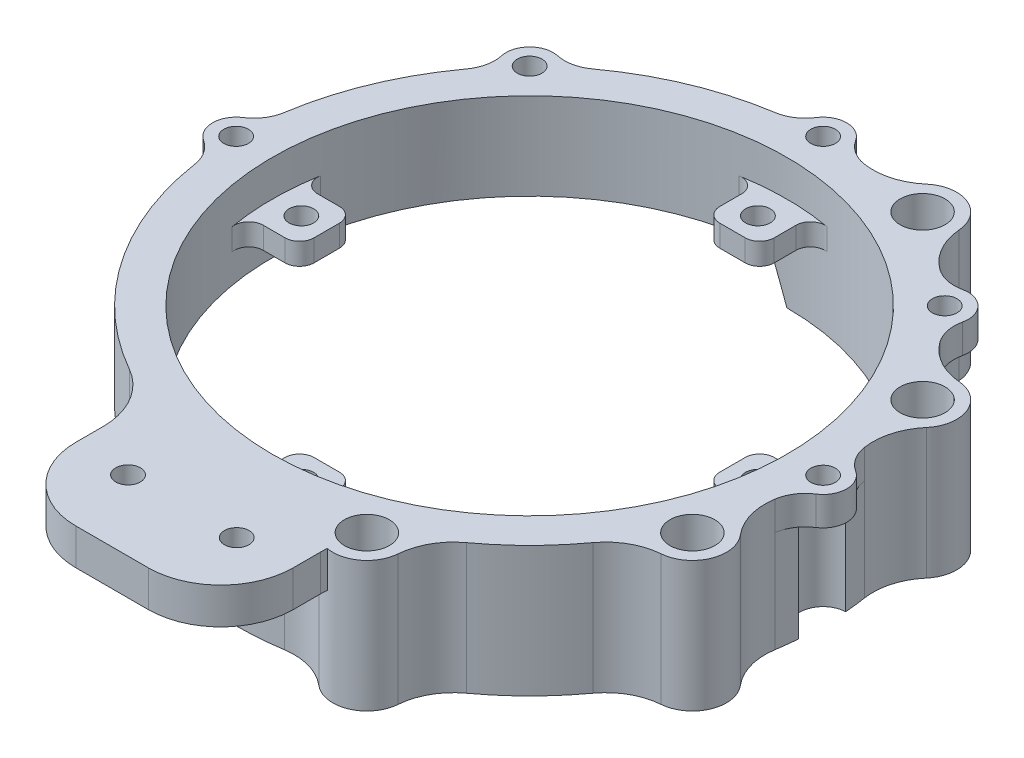
SolidWorks part; units mm, degrees
ref_plane "Alzado" through (0, 0, 0) normal (0, 0, 1) x (1, 0, 0)
ref_plane "Planta" through (0, 0, 0) normal (0, 1, 0) x (1, 0, 0)
ref_plane "Vista lateral" through (0, 0, 0) normal (1, 0, 0) x (0, 0, -1)
sketch "Croquis1" plane through (0, 0, 0) normal (0, 1, 0) x (1, 0, 0)
  circle A0 centre (0, 0) radius 35.5
  circle A1 centre (0, 0) radius 40.5
  dimension "D1" = 71
  dimension "D2" = 5
extrude "Saliente-Extruir1" add sketch "Croquis1" along normal mid plane 18
sketch "Croquis2" plane through (0, 9, 0) normal (0, -1, 0) x (1, 0, 0)
  line L0 (-15, 37.6198) -> (-15, 57.6198)
  line L1 (-15, 57.6198) -> (15, 57.6198)
  line L2 (15, 57.6198) -> (15, 37.6198)
  line L3 (0, 0) -> (0, 98.2113) construction
  circle A0 centre (0, 0) radius 40.5 construction
  arc A1 (15, 37.6198) -> (-15, 37.6198) centre (0, 0) ccw
  circle A2 centre (-7.5, 47.9166) radius 1.7
  circle A3 centre (7.5, 47.9166) radius 1.7
  circle A6 centre (0, 0) radius 48.5
  circle A7 centre (0, 0) radius 48.5 construction
  point P7 (0, 57.6198)
  dimension "D5" = 3.4
  dimension "D1" = 30
  dimension "D2" = 20
  dimension "D3" = 8
  dimension "D4" = 15
extrude "Saliente-Extruir2" add sketch "Croquis2" along normal blind 5
fillet "Redondeo1" radius 10 4 edges at (15, 6.5, 37.6198) (-15, 6.5, 37.6198) (-15, 6.5, 57.6198) (15, 6.5, 57.6198)
ref_plane "Plano1" through (0, 1, 0) normal (0, -1, 0) x (-1, 0, 0)
sketch "Croquis4" plane through (0, 1, 0) normal (0, -1, 0) x (-1, 0, 0)
  line L0 (0, -35.5) -> (0, 0) construction
  line L1 (-3.75, -35.3014) -> (-3.75, -28)
  line L2 (-3.75, -28) -> (3.75, -28)
  line L3 (3.75, -35.3014) -> (3.75, -28)
  circle A0 centre (0, 0) radius 35.5 construction
  arc A1 (-3.75, -35.3014) -> (3.75, -35.3014) centre (0, 0) ccw
  circle A2 centre (0, 0) radius 25 construction
  circle A3 centre (0, -31.5) radius 1.7
  circle A4 centre (0, 0) radius 31.5 construction
  point P12 (0, -28)
  dimension "D1" = 3.4
  dimension "D5" = 50
  dimension "D6" = 6.5
  dimension "D3" = 7.5
  dimension "D4" = 3.75
extrude "Saliente-Extruir3" add sketch "Croquis4" against normal blind 3
fillet "Redondeo2" radius 2 4 edges at (-3.75, 2.5, 35.3014) (3.75, 2.5, 28) (-3.75, 2.5, 28) (3.75, 2.5, 35.3014)
pattern_circular "MatrizC1" count 4 over 360 about axis through (0, 9, 0) along (0, 1, 0) of "Saliente-Extruir3", "Redondeo2"
hole_wizard "Refrentado para tornillo con cabeza plana de M31" positions "Croquis5" profile "Croquis7" counterbore size "M3" standard "ISO" end condition through all
sketch "Croquis5" plane through (0, -9, 0) normal (0, -1, 0) x (-1, 0, 0)
  circle A0 centre (0, 0) radius 40.5 construction
  point P0 (0, 40.5)
sketch "Croquis7" plane through (0, -9, -40.5) normal (1, 0, 0) x (0, 0, -1)
  line L0 (0, 0) -> (0, 18)
  line L1 (0, 18) -> (1.7, 18)
  line L3 (1.7, 18) -> (1.7, 14)
  line L4 (1.7, 14) -> (3.25, 14)
  line L5 (3.25, 14) -> (3.25, 0)
  line L7 (3.25, 0) -> (0, 0)
  line L11 (0, -6.35) -> (0, 107.95) construction
  dimension "Diámetro de taladro hasta el siguiente" = 3.4
  dimension "Profundidad de taladro hasta el siguiente" = 18
  dimension "Diámetro de refrentado" = 6.5
  dimension "Profundidad de refrentado" = 14
sketch "Croquis8" plane through (0, 5, 0) normal (0, -1, 0) x (1, 0, 0)
  circle A0 centre (0, -40.5) radius 3.25
  circle A2 centre (0, -40.5) radius 1.7
extrude "Saliente-Extruir4" add sketch "Croquis8" against normal up to surface (4 mm away) up to face at (0, 9, 27.8312)
pattern_circular "MatrizC2" count 3 every 45 about axis through (0, -9, 0) along (0, 1, 0) of "Saliente-Extruir4", "Refrentado para tornillo con cabeza plana de M31"
mirror "Simetría1" about plane through (0, 0, 0) normal (1, 0, 0) of "MatrizC2"
fillet "Redondeo4" radius 5 10 edges at (-40.3696, 7, -3.2474) (-40.3696, 7, 3.2474) (-30.8419, 7, -26.2494) (-26.2494, 7, -30.8419) (-3.2474, 7, -40.3696) (3.2474, 7, -40.3696) (40.3696, 7, -3.2474) (40.3696, 7, 3.2474) (30.8419, 7, -26.2494) (26.2494, 7, -30.8419)
sketch "Croquis13" plane through (0, -9, 0) normal (0, -1, 0) x (1, 0, 0)
  line L0 (0, 40.5) -> (0, 35.5)
  line L1 (0, -35.5) -> (0, -40.5)
  arc A0 (0, 40.5) -> (0, -40.5) centre (0, 0) ccw
  arc A1 (0, 35.5) -> (0, -35.5) centre (0, 0) ccw
  dimension "D1" = 81
extrude "Cortar-Extruir5" cut sketch "Croquis13" against normal blind 6
chamfer "Chaflán1" distance 6 angle 20 2 edges at (0, -3, -36.375) (0, -3, 38) first distance on face at (0, -6, -36.375) first distance on face at (0, -6, 38)
sketch "Croquis14" plane through (0, -9, 0) normal (0, -1, 0) x (1, 0, 0)
  line L0 (19.8796, 0) -> (0, 0) construction
  line L1 (0, 0) -> (11.2108, 27.0652) construction
  line L2 (0, 0) -> (11.2108, -27.0652) construction
  circle A0 centre (15.8814, 38.341) radius 1.7
  circle A1 centre (0, 0) radius 40.5 construction
  circle A8 centre (38.1004, 15.9815) radius 1.7
  circle A9 centre (38.0004, -15.5403) radius 1.7
  circle A10 centre (15.6401, -37.7585) radius 1.7
  point P16 (0, 0)
  point P18 (0, 0)
  point P19 (0.0012, 0.3412)
  dimension "D2" = 3.4
  dimension "D3" = 81
  dimension "D1" = 4
  dimension "D4" = 41.5
  dimension "D5" = 67.5
extrude "Cortar-Extruir6" cut sketch "Croquis14" against normal up to surface (18 mm away) up to face at (0, 9, -0.9354)
sketch "Croquis15" plane through (0, -9, 0) normal (0, -1, 0) x (1, 0, 0)
  circle A0 centre (15.8814, 38.341) radius 4.7
  arc A2 (14.2354, 37.9157) -> (16.7445, 36.8764) centre (15.8814, 38.341) ccw construction
  circle A3 centre (15.8814, 38.341) radius 1.7
  arc A4 (14.2354, 37.9157) -> (16.7445, 36.8764) centre (15.8814, 38.341) ccw construction
  dimension "D1" = 3
  dimension "D2" = 3.4
extrude "Saliente-Extruir5" add sketch "Croquis15" against normal up to surface (18 mm away) up to face at (5.7609, 9, -0.6169)
sketch "Croquis16" plane through (0, 9, 0) normal (0, 1, 0) x (1, 0, 0)
  circle A0 centre (15.8814, -38.341) radius 3.1
  dimension "D1" = 6.2
extrude "Cortar-Extruir9" cut sketch "Croquis16" against normal blind 10 contours A0
pattern_circular "MatrizC3" count 4 over 135 about axis through (0, 9, 0) along (0, 1, 0) of "Saliente-Extruir5", "Cortar-Extruir9"
fillet "Redondeo5" radius 8.3 8 edges at (19.5862, -2.5, 35.449) (11.2166, -2.5, 38.9158) (35.449, 0, 19.5862) (38.9158, 0, 11.2166) (19.5862, 0, -35.449) (11.2166, 0, -38.9158) (38.9158, 0, -11.2166) (35.449, 0, -19.5862)
